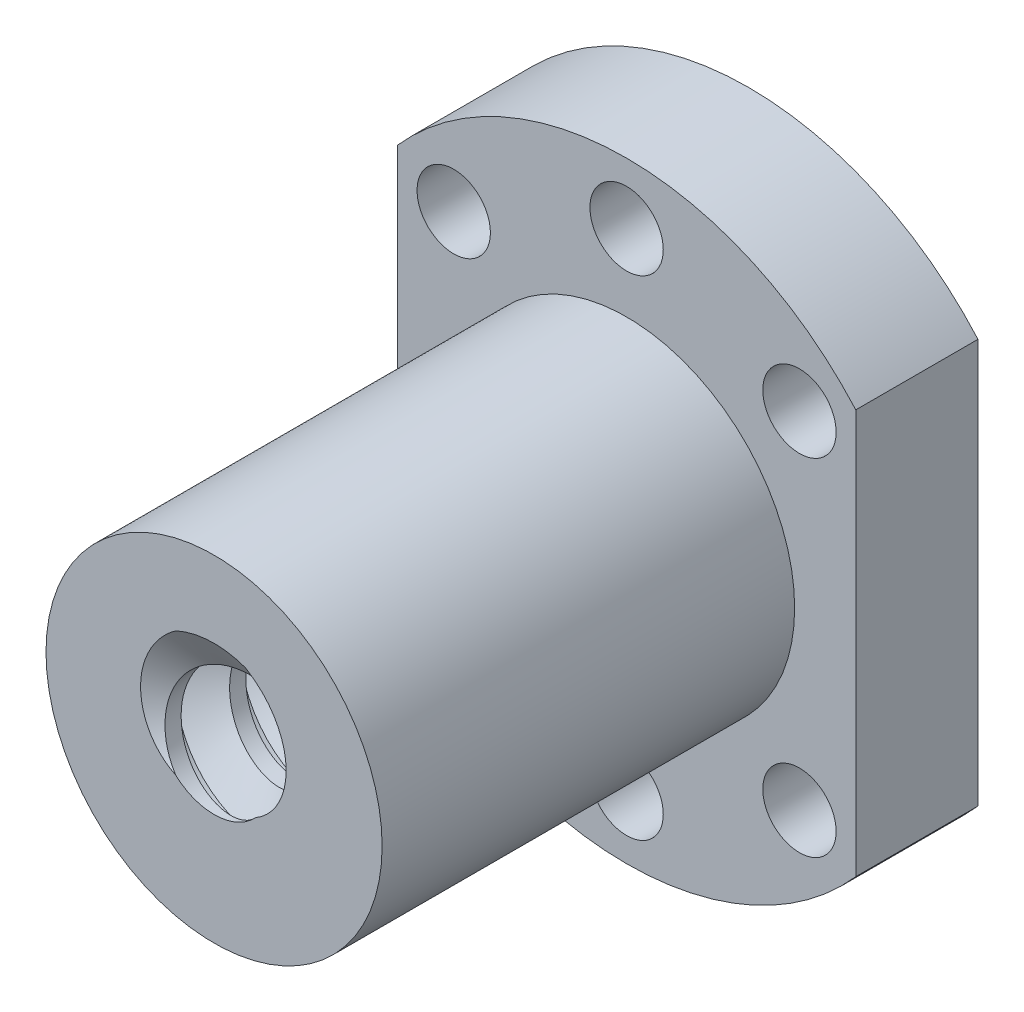
SolidWorks part; units mm, degrees
ref_plane "Front Plane" through (0, 0, 0) normal (0, 0, 1) x (1, 0, 0)
ref_plane "Top Plane" through (0, 0, 0) normal (0, 1, 0) x (1, 0, 0)
ref_plane "Right Plane" through (0, 0, 0) normal (1, 0, 0) x (0, 0, -1)
sketch "Sketch1" plane through (0, 0, 0) normal (0, 0, 1) x (1, 0, 0)
  line L6 (15, -13.2288) -> (15, 13.2288)
  line L8 (-15, -13.2288) -> (-15, 13.2288)
  line L9 (15, -13.2288) -> (-15, 13.2288) construction
  line L10 (15, 13.2288) -> (-15, -13.2288) construction
  arc A3 (-15, -13.2288) -> (15, -13.2288) centre (0, 0) ccw
  arc A4 (15, 13.2288) -> (-15, 13.2288) centre (0, 0) ccw
  dimension "D1" = 40
  dimension "D2" = 30
extrude "Boss-Extrude1" add sketch "Sketch1" along normal blind 8
sketch "Sketch2" plane through (0, 0, 8) normal (0, 0, 1) x (1, 0, 0)
  circle A0 centre (0, 0) radius 11
  dimension "D1" = 22
extrude "Boss-Extrude2" add sketch "Sketch2" along normal blind 27
sketch "Sketch3" plane through (0, 0, 35) normal (0, 0, 1) x (1, 0, 0)
  circle A0 centre (0, 0) radius 6
  dimension "D1" = 12
extrude "Cut-Extrude1" cut sketch "Sketch3" against normal through all
sketch "Sketch4" plane through (0, 0, 8) normal (0, 0, 1) x (1, 0, 0)
  circle A0 centre (0, 0) radius 16
  circle A1 centre (0, 16) radius 2.4
  circle A2 centre (-11.3137, 11.3137) radius 2.4
  circle A3 centre (11.3137, 11.3137) radius 2.4
  circle A4 centre (11.3137, -11.3137) radius 2.4
  circle A5 centre (0, -16) radius 2.4
  circle A6 centre (-11.3137, -11.3137) radius 2.4
  point P17 (0, 0)
  dimension "D1" = 32
  dimension "D2" = 4.8
  dimension "D3" = 45
  dimension "D4" = 45
  dimension "D5" = 2
extrude "Cut-Extrude2" cut sketch "Sketch4" against normal through all contours A0 A1 | A0 A1 | A0 A3 | A0 A3 | A0 A4 | A0 A4 | A0 A5 | A0 A5 | A0 A6 | A0 A6 | A2 region at (10.571, 10.571, 8) region at (12.0106, 12.0106, 8) region at (12.0106, -12.0106, 8) region at (10.571, -10.571, 8) region at (0, 14.9497, 8) region at (0, 16.9855, 8) region at (0, -16.9855, 8) region at (0, -14.9497, 8) region at (-12.0106, -12.0106, 8) region at (-10.571, -10.571, 8)
thread "Thread1" pitch 4.2333 method extrude trim with start face yes trim with end face yes profile "Thread Profile1" start angle 0, offset 5, length 0, pitch 4.2333, diameter 12
ref_plane "Plane1" through (-6, 0, 40) normal (0, -1, 0) x (-1, 0, 0)
sketch "Thread Profile1" plane through (-6, 0, 40) normal (0, -1, 0) x (-1, 0, 0)
  line L0 (0, 0) -> (0, 4.2333) construction
  line L11 (0, 0) -> (0, 3.7042)
  line L12 (0, 3.7042) -> (-2.2914, 2.3812)
  line L13 (-2.2914, 2.3812) -> (-2.2914, 1.3229)
  line L15 (-2.2914, 1.3229) -> (0, 0)
  line L17 (-2.2914, 1.8521) -> (0, 1.8521) construction
  point P2 (0, 0)
  dimension "Pitch" = 4.2333
  dimension "Profile_Angle" = 60
  dimension "Profile_Land" = 1.0583
  dimension "Profile_Height" = 2.2914
